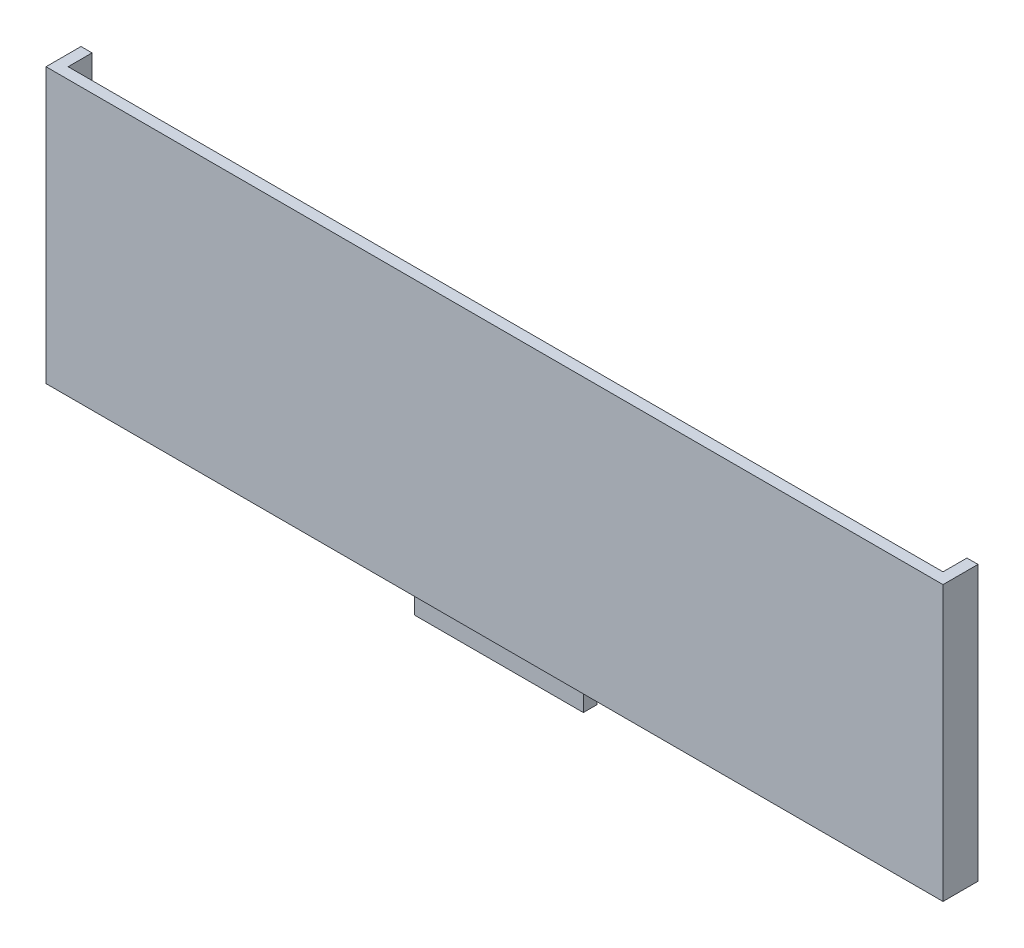
SolidWorks part; units mm, degrees
ref_plane "Front Plane" through (0, 0, 0) normal (0, 0, 1) x (1, 0, 0)
ref_plane "Top Plane" through (0, 0, 0) normal (0, 1, 0) x (1, 0, 0)
ref_plane "Right Plane" through (0, 0, 0) normal (1, 0, 0) x (0, 0, -1)
sketch "Sketch1" plane through (0, 0, 0) normal (0, 1, 0) x (1, 0, 0)
  line L0 (-72.3803, 64.0522) -> (-69.3803, 64.0522)
  line L2 (-72.3803, 64.0522) -> (-72.3803, 54.5522)
  line L3 (-72.3803, 54.5522) -> (171.1197, 54.5522)
  line L4 (171.1197, 64.0522) -> (171.1197, 54.5522)
  line L5 (-69.3803, 64.0522) -> (-69.3803, 57.5522)
  line L6 (-69.3803, 57.5522) -> (168.1197, 57.5522)
  line L7 (168.1197, 57.5522) -> (168.1197, 64.0522)
  line L8 (168.1197, 64.0522) -> (171.1197, 64.0522)
  line L9 (-69.3803, 64.0522) -> (168.1197, 64.0522)
  dimension "D1" = 243.5
  dimension "D2" = 9.5
  dimension "D3" = 3
  dimension "D4" = 3
  dimension "D5" = 6.5
extrude "Boss-Extrude1" add sketch "Sketch1" along normal blind 3 contours L8 L7 L6 L5 L0 L2 L3 L4 | L9 L5 L6 L7 region at (49.3697, 0, -56.2929) region at (49.3697, 0, -60.8022)
extrude "Boss-Extrude2" add sketch "Sketch1<3>" along normal blind 74.5 contours L8 L7 L6 L5 L0 L2 L3 L4 region at (49.3697, 0, -56.2929)
sketch "Sketch1<3>" plane through (0, 0, 0) normal (0, 1, 0) x (1, 0, 0) same geometry as "Sketch1"
sketch "Sketch2" plane through (0, 0, 0) normal (0, -1, 0) x (1, 0, 0)
  line L1 (25.0662, -57.1503) -> (70.8884, -57.1503)
  line L2 (25.0662, -57.1503) -> (25.0662, -60.8212)
  line L3 (25.0662, -60.8212) -> (70.8884, -60.8212)
  line L4 (70.8884, -57.1503) -> (70.8884, -60.8212)
extrude "Boss-Extrude3" add sketch "Sketch2" along normal blind 7
